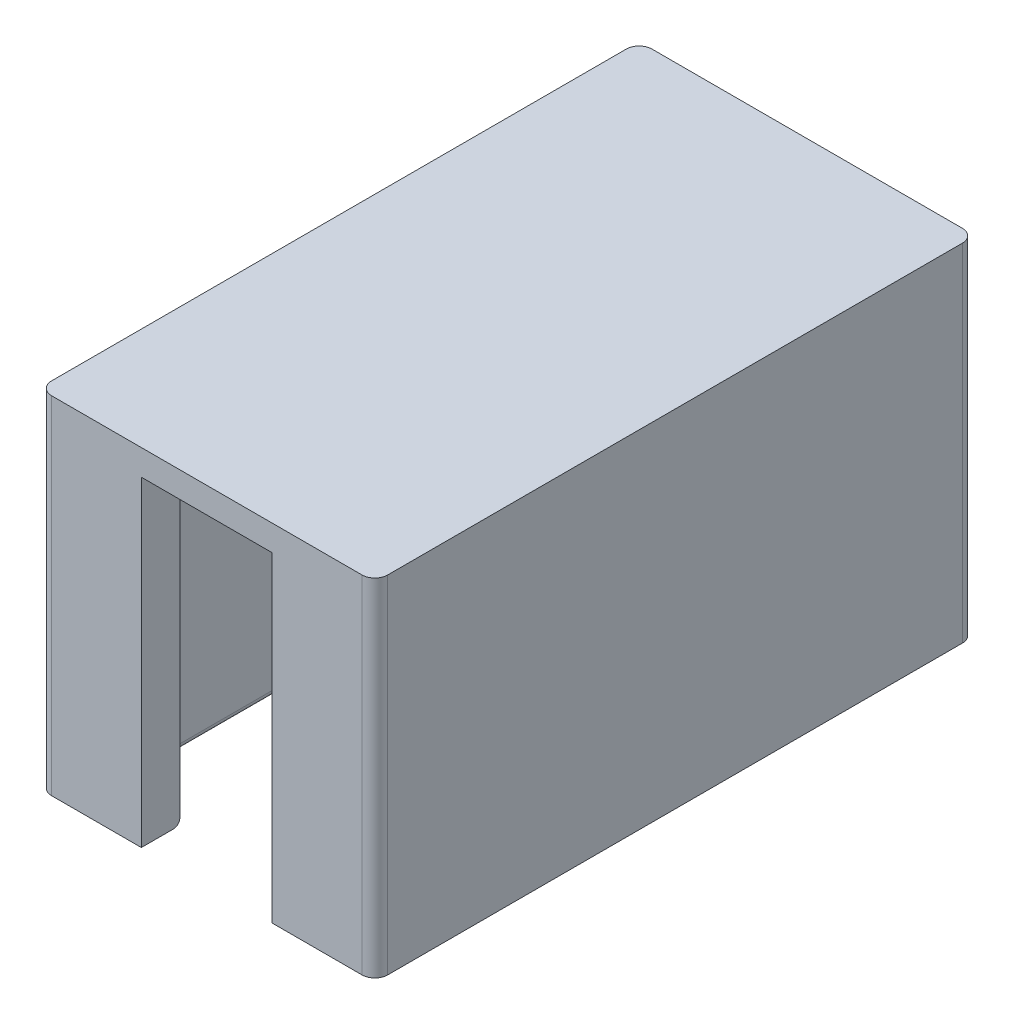
SolidWorks part; units mm, degrees
ref_plane "Front Plane" through (0, 0, 0) normal (0, 0, 1) x (1, 0, 0)
ref_plane "Top Plane" through (0, 0, 0) normal (0, 1, 0) x (1, 0, 0)
ref_plane "Right Plane" through (0, 0, 0) normal (1, 0, 0) x (0, 0, -1)
sketch "Sketch1" plane through (0, 0, 0) normal (0, 1, 0) x (1, 0, 0)
  line L5 (0, 0) -> (26.2, 0)
  line L6 (0, 0) -> (0, 46.8)
  line L7 (0, 46.8) -> (26.2, 46.8)
  line L8 (26.2, 0) -> (26.2, 46.8)
  line L9 (3, 3) -> (23.2, 3)
  line L10 (3, 3) -> (3, 43.8)
  line L11 (3, 43.8) -> (23.2, 43.8)
  line L12 (23.2, 3) -> (23.2, 43.8)
  dimension "D1" = 20.2
  dimension "D2" = 40.8
  dimension "D3" = 3
  dimension "D4" = 3
  dimension "D5" = 3
  dimension "D6" = 3
extrude "Boss-Extrude1" add sketch "Sketch1" along normal blind 25
sketch "Sketch3" plane through (0, 0, 0) normal (0, 0, 1) x (1, 0, 0)
  line L0 (0, 0) -> (26.2, 0) construction
  line L1 (8, 0) -> (18.2, 0)
  line L2 (8, 0) -> (8, 25)
  line L3 (8, 25) -> (18.2, 25)
  line L4 (18.2, 0) -> (18.2, 25)
  line L5 (0, 25) -> (26.2, 25) construction
  line L6 (0, 25) -> (0, 0) construction
  line L7 (26.2, 25) -> (26.2, 0) construction
  dimension "D1" = 8
  dimension "D2" = 8
extrude "Cut-Extrude1" cut sketch "Sketch3" against normal blind 10 contours L2 L1 L4 L3
fillet "Fillet1" radius 0.5 10 edges at (5.5, 25, -3) (3, 25, -23.4) (13.1, 25, -43.8) (20.7, 25, -3) (23.2, 25, -23.4) (5.5, 0, -3) (3, 0, -23.4) (13.1, 0, -43.8) (23.2, 0, -23.4) (20.7, 0, -3)
sketch "Sketch4" plane through (0, 25, 0) normal (0, 1, 0) x (1, 0, 0)
  line L1 (0, 0) -> (26.2, 0)
  line L2 (0, 0) -> (0, 46.8)
  line L3 (0, 46.8) -> (26.2, 46.8)
  line L4 (26.2, 0) -> (26.2, 46.8)
extrude "Boss-Extrude2" add sketch "Sketch4" along normal blind 2
fillet "Fillet2" radius 1 4 edges at (26.2, 13.5, -46.8) (0, 13.5, -46.8) (26.2, 13.5, 0) (0, 13.5, 0)
sketch "Sketch5" plane through (0, 0, -46.8) normal (0, 0, -1) x (-1, 0, 0)
  line L0 (-25.2, 0) -> (-1, 0) construction
  line L1 (-18.2, 0) -> (-8, 0)
  line L2 (-18.2, 0) -> (-18.2, 24.5)
  line L4 (-8, 0) -> (-8, 24.5)
  line L6 (-18.2, 24.5) -> (-8, 24.5)
  line L7 (-25.2, 27) -> (-1, 27) construction
  dimension "D1" = 8
  dimension "D2" = 8
  dimension "D3" = 2.5
extrude "Cut-Extrude3" cut sketch "Sketch5" against normal blind 5
